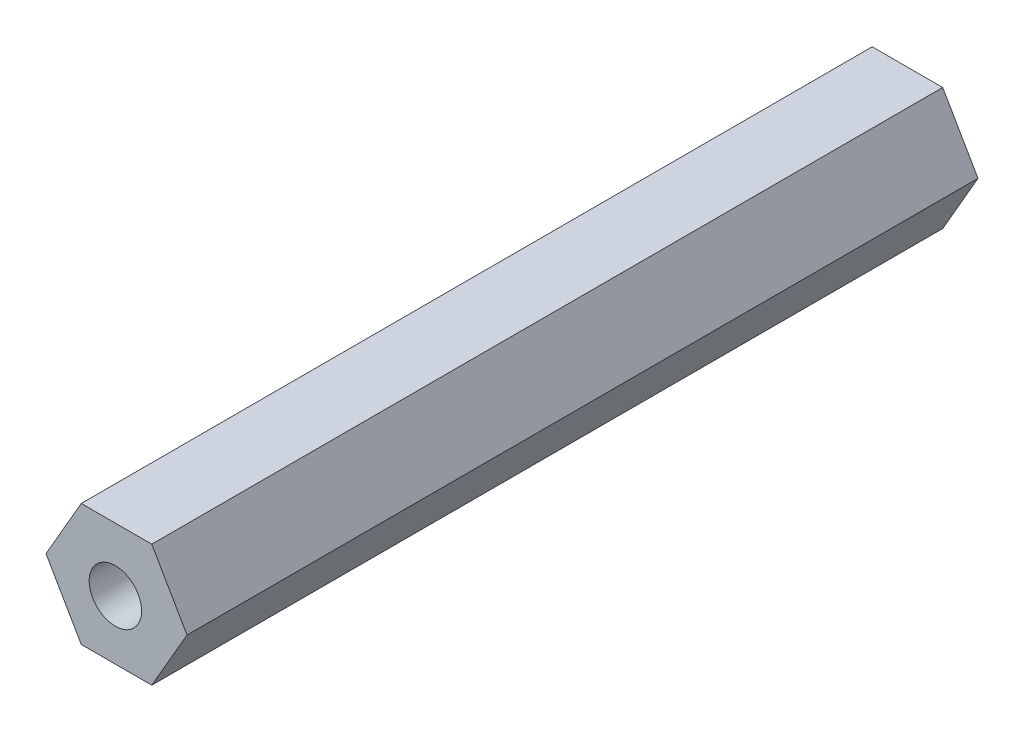
SolidWorks part; units mm, degrees
note: The reader was unsure of these and kept them because the rebuilt part matched: shared geometry of "Sketch1<2>".
other "Defeature"
material "6061 Alloy"
ref_plane "Front Plane" through (0, 0, 0) normal (0, 0, 1) x (1, 0, 0)
ref_plane "Top Plane" through (0, 0, 0) normal (0, 1, 0) x (1, 0, 0)
ref_plane "Right Plane" through (0, 0, 0) normal (1, 0, 0) x (0, 0, -1)
sketch "Sketch1" plane through (0, 0, 0) normal (0, 0, 1) x (1, 0, 0)
  line L1 (3.6373, 0) -> (1.8187, 3.15)
  line L2 (1.8187, 3.15) -> (-1.8187, 3.15)
  line L3 (-1.8187, 3.15) -> (-3.6373, 0)
  line L4 (-3.6373, 0) -> (-1.8187, -3.15)
  line L5 (-1.8187, -3.15) -> (1.8187, -3.15)
  line L6 (1.8187, -3.15) -> (3.6373, 0)
  circle A0 centre (0, 0) radius 3.15 construction
  dimension "D1" = 6.3
extrude "Boss-Extrude1" add sketch "Sketch1" against normal mid plane 50.8
hole_wizard "#6-32 Tapped Hole8" positions "3DSketch13" profile "Sketch27" tap size "#6-32" standard "Ansi Inch" end condition through all
sketch3d "3DSketch13"
  point P0 (-0.0588, -0.1018, 25.4)
  dimension "D1" = 3.58
  dimension "D2" = 3.58
sketch "Sketch27" plane through (-0.0588, -0.1018, 25.4) normal (1, 0, 0) x (0, -1, 0)
  line L0 (0, 0) -> (0, 50.8)
  line L1 (0, 50.8) -> (1.3525, 50.8)
  line L2 (1.3525, 50.8) -> (1.3525, 0)
  line L5 (1.3525, 0) -> (0, 0)
  line L11 (0, -6.35) -> (0, 107.95) construction
  dimension "Thru Tap Drill Dia." = 2.7051
  dimension "Thru Tap Drill Depth" = 50.8
cosmetic thread "Hole Thread12" parameters "D2"=3.5052
chamfer "Chamfer1" distance 0.5 angle 45 1 edges at (1.2938, -0.1018, 25.4)
chamfer "Chamfer2" distance 0.5 angle 45 1 edges at (1.2938, -0.1018, -25.4)
sketch "Sketch15" plane through (0, 0, 25.4) normal (0, 0, 1) x (1, 0, 0)
  circle A0 centre (0, 0) radius 1.5
  dimension "D1" = 3
extrude "Cut-Extrude1" [suppressed] cut sketch "Sketch15" against normal through all
sketch "Sketch28" plane through (0, 0, 25.4) normal (0, 0, 1) x (1, 0, 0)
extrude "Cut-Extrude2" cut sketch "Sketch1<2>" against normal blind 10 from surface at 25.4 starting at face at (1.7938, -0.1018, 25.4)
sketch "Sketch1<2>" plane through (0, 0, 0) normal (0, 0, 1) x (1, 0, 0) same geometry as "Sketch1"
